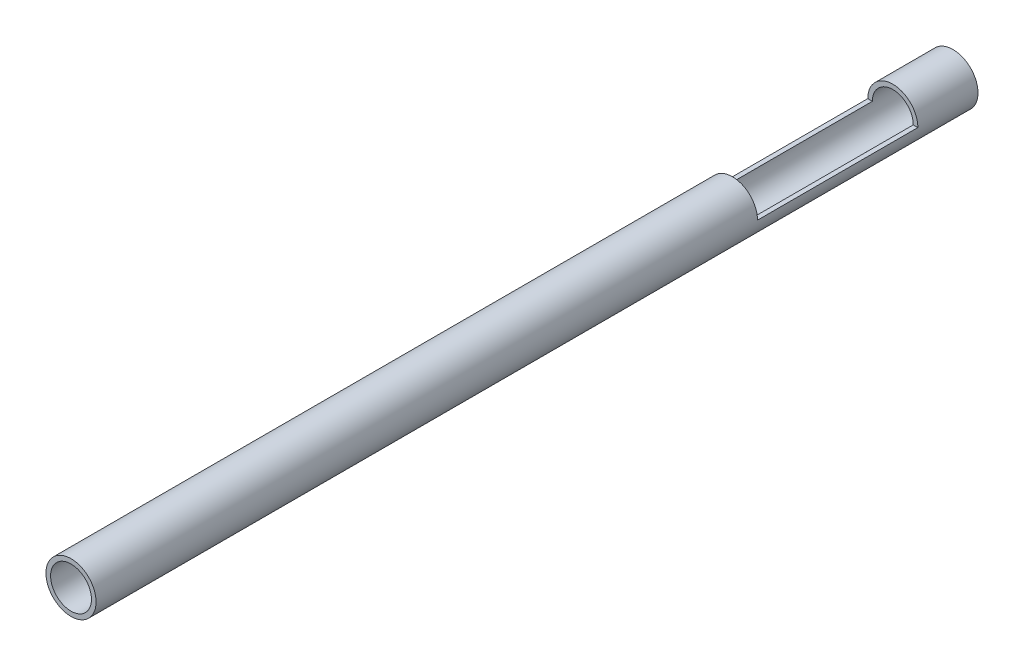
SolidWorks part; units mm, degrees
ref_plane "Front" through (0, 0, 0) normal (0, 0, 1) x (1, 0, 0)
ref_plane "Top" through (0, 0, 0) normal (0, 1, 0) x (1, 0, 0)
ref_plane "Right" through (0, 0, 0) normal (1, 0, 0) x (0, 0, -1)
sketch "Sketch2" plane through (0, 0, 0) normal (0, 0, 1) x (1, 0, 0)
  circle A0 centre (0, 0) radius 12.954
  circle A1 centre (0, 0) radius 15.875
  dimension "D1" = 31.75
  dimension "D2" = 25.908
extrude "Boss-Extrude1" add sketch "Sketch2" along normal blind 558.8
sketch "Sketch3" plane through (0, 0, 0) normal (0, 1, 0) x (1, 0, 0)
  line L0 (15.875, 0) -> (-15.875, 0) construction
  line L1 (-25.4, -38.1) -> (25.4, -38.1)
  line L2 (-25.4, -38.1) -> (-25.4, -139.7)
  line L3 (-25.4, -139.7) -> (25.4, -139.7)
  line L4 (25.4, -38.1) -> (25.4, -139.7)
  line L5 (-25.4, -38.1) -> (25.4, -139.7) construction
  line L6 (-25.4, -139.7) -> (25.4, -38.1) construction
  line L7 (0, 0) -> (0, -161.8795) construction
  point P4 (0, -88.9)
  dimension "D1" = 101.6
  dimension "D2" = 38.1
  dimension "D3" = 25.4
  dimension "D4" = 25.4
extrude "Cut-Extrude1" cut sketch "Sketch3" along normal up to next
